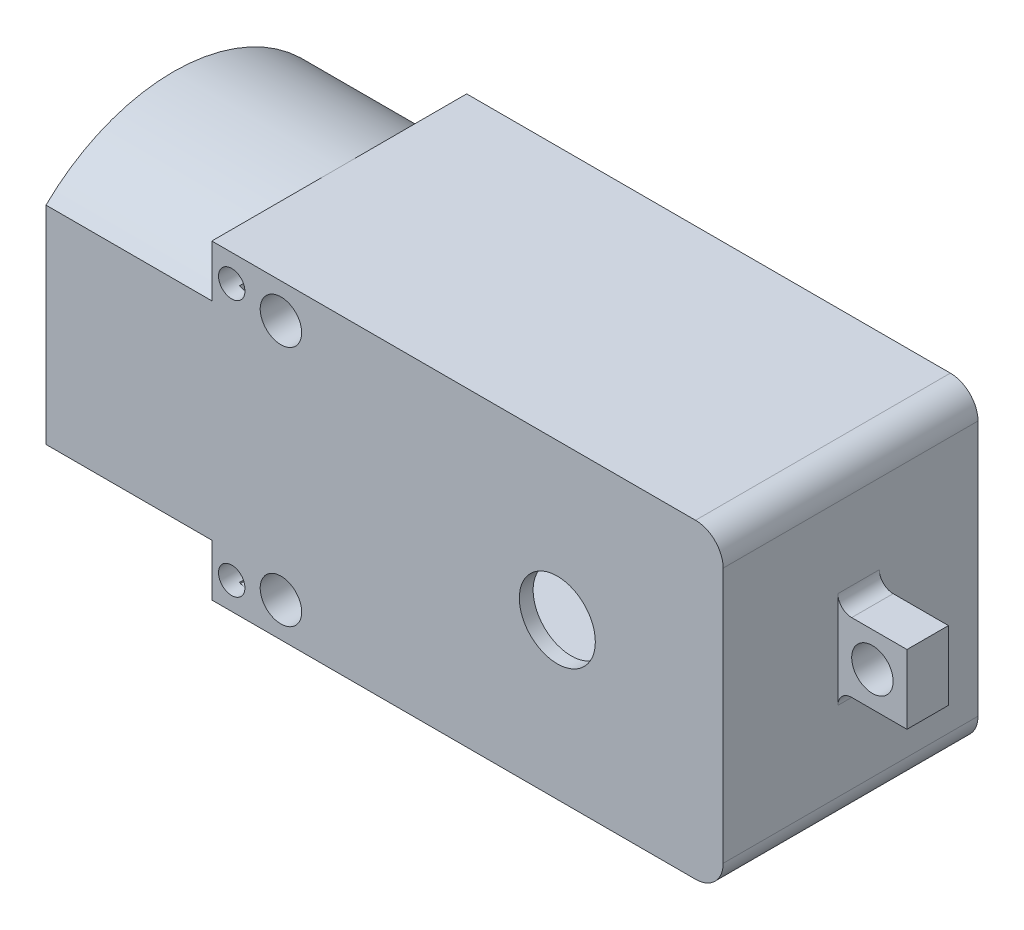
SolidWorks part; units mm, degrees
ref_plane "Front Plane" through (0, 0, 0) normal (0, 0, 1) x (1, 0, 0)
ref_plane "Top Plane" through (0, 0, 0) normal (0, 1, 0) x (1, 0, 0)
ref_plane "Right Plane" through (0, 0, 0) normal (1, 0, 0) x (0, 0, -1)
sketch "Sketch1" plane through (0, 0, 0) normal (0, 0, 1) x (1, 0, 0)
  line L1 (17.5, -11.25) -> (-17.5, -11.25)
  line L2 (19.5, -9.25) -> (19.5, 9.25)
  line L3 (17.5, 11.25) -> (-17.5, 11.25)
  line L4 (-17.5, -11.25) -> (-17.5, 11.25)
  line L5 (0, 11.25) -> (0, -11.25) construction
  line L6 (19.5, 0) -> (-17.5, 0) construction
  arc A0 (17.5, -11.25) -> (19.5, -9.25) centre (17.5, -9.25) ccw
  arc A1 (19.5, 9.25) -> (17.5, 11.25) centre (17.5, 9.25) ccw
  circle A2 centre (-12.5, 8.75) radius 1.5
  circle A3 centre (-12.5, -8.75) radius 1.5
  point P0 (0, 0)
  dimension "D1" = 2
  dimension "D4" = 3
  dimension "D6" = 17.5
  dimension "D2" = 22.5
  dimension "D3" = 37
  dimension "D5" = 5
extrude "Boss-Extrude1" add sketch "Sketch1" along normal mid plane 18.44
ref_plane "Plane1" through (0, 0, -0.58) normal (0, 0, 1) x (1, 0, 0)
sketch "Sketch2" plane through (-17.5, 0, 0) normal (-1, 0, 0) x (0, 0, 1)
  line L0 (9.22, -7.5) -> (9.22, 7.5)
  line L1 (-9.22, 11.25) -> (-9.22, -11.25) construction
  line L2 (9.22, 11.25) -> (9.22, -11.25) construction
  line L3 (0, 11.25) -> (0, -11.25) construction
  line L4 (9.22, 11.25) -> (-9.22, 11.25) construction
  line L5 (9.22, -11.25) -> (-9.22, -11.25) construction
  line L6 (-9.22, 0) -> (9.22, 0) construction
  line L7 (-9.22, -7.5) -> (-9.22, 7.5)
  arc A0 (9.22, 7.5) -> (-9.22, 7.5) centre (0, -1.9595) ccw
  arc A1 (9.22, -7.5) -> (-9.22, -7.5) centre (0, 1.9595) cw
  point P5 (9.22, 0)
  point P14 (0, 0)
  dimension "D1" = 15
extrude "Boss-Extrude2" add sketch "Sketch2" along normal blind 12
shell "Shell1" thickness 1 removed face at (-29.5, 0, 0)
sketch "Sketch3" plane through (-17.5, 0, 0) normal (-1, 0, 0) x (0, 0, 1)
  line L2 (-9.22, 7.5) -> (-9.22, -7.5)
  line L3 (9.22, -7.5) -> (9.22, 7.5)
  line L4 (-9.22, 7.5) -> (-9.22, -7.5)
  line L5 (9.22, -7.5) -> (9.22, 7.5)
  circle A0 centre (0, 0) radius 1.5
  arc A2 (9.22, 7.5) -> (-9.22, 7.5) centre (0, -1.9595) ccw
  arc A3 (-9.22, -7.5) -> (9.22, -7.5) centre (0, 1.9595) ccw
  arc A4 (9.22, 7.5) -> (-9.22, 7.5) centre (0, -1.9595) ccw
  arc A5 (-9.22, -7.5) -> (9.22, -7.5) centre (0, 1.9595) ccw
  dimension "D2" = 3
  dimension "D1" = 0
extrude "Boss-Extrude3" add sketch "Sketch3" along normal blind 1
sketch "Sketch6" plane through (0, 0, -0.58) normal (0, 0, 1) x (1, 0, 0)
  line L0 (19.5, 2.5) -> (24.5, 2.5)
  line L1 (19.5, -9.25) -> (19.5, 9.25) construction
  line L2 (24.5, 2.5) -> (24.5, -2.5)
  line L3 (24.5, -2.5) -> (19.5, -2.5)
  line L4 (24.5, 0) -> (-29.5, 0) construction
  line L5 (-29.5, 7.5) -> (-29.5, -7.5) construction
  line L6 (19.5, 2.5) -> (19.5, -2.5)
  line L7 (22, -2.5) -> (22, 2.5) construction
  circle A0 centre (22, 0) radius 1.5
  dimension "D3" = 3
  dimension "D1" = 5
  dimension "D2" = 5
extrude "Boss-Extrude4" add sketch "Sketch6" against normal blind 1.5 and the other way blind 1.5
sketch "Sketch7" plane through (0, 0, 9.22) normal (0, 0, 1) x (1, 0, 0)
  line L0 (-29.5, 0) -> (24.5, 0) construction
  line L1 (-29.5, -7.5) -> (-29.5, 7.5) construction
  line L2 (24.5, -2.5) -> (24.5, 2.5) construction
  circle A0 centre (7.5, 0) radius 2.75
  circle A1 centre (-12.5, 8.75) radius 1.5 construction
  circle A2 centre (22, 0) radius 1.5 construction
  dimension "D1" = 20
  dimension "D2" = 5.5
  dimension "D3" = 14.5
extrude "Cut-Extrude1" cut sketch "Sketch7" against normal blind 3
fillet "Fillet1" radius 1 2 edges at (19.5, -2.5, -0.58) (19.5, 2.5, -0.58)
sketch "Sketch8" plane through (0, 0, -0.58) normal (0, 0, 1) x (1, 0, 0)
  line L0 (17.5, 11.25) -> (-17.5, 11.25) construction
  line L1 (19.5, 0) -> (-18.5, 0) construction
  line L2 (19.5, -9.25) -> (19.5, 9.25) construction
  line L3 (-18.5, 7.0684) -> (-18.5, -7.0684) construction
  circle A0 centre (-16.062, 9.294) radius 0.956
  circle A1 centre (-16.062, -9.294) radius 0.956
  point P2 (-16.062, 10.25)
  dimension "D1" = 1
extrude "Cut-Extrude2" cut sketch "Sketch8" against normal blind 20 and the other way blind 20
